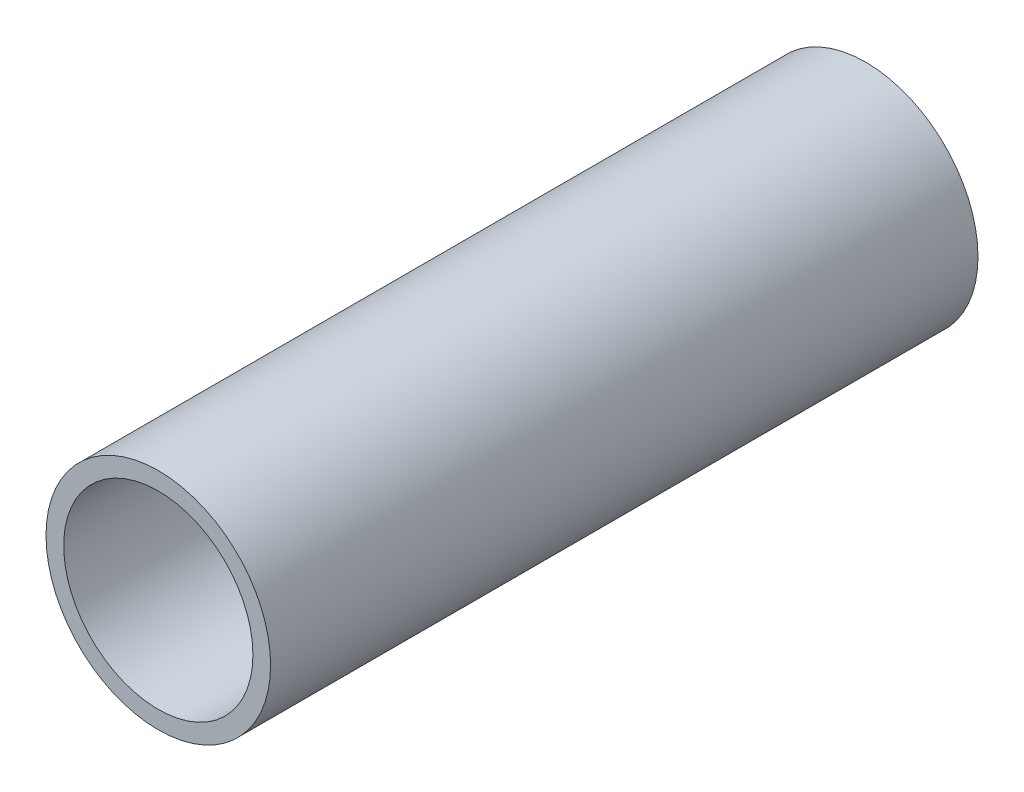
SolidWorks part; units mm, degrees
material "Hexcel AS4C (3000 Filaments)"
ref_plane "Front Plane" through (0, 0, 0) normal (0, 0, 1) x (1, 0, 0)
ref_plane "Top Plane" through (0, 0, 0) normal (0, 1, 0) x (1, 0, 0)
ref_plane "Right Plane" through (0, 0, 0) normal (1, 0, 0) x (0, 0, -1)
sketch "Sketch1" plane through (0, 0, 0) normal (0, 0, 1) x (1, 0, 0)
  circle A0 centre (0, 0) radius 12.7
  circle A1 centre (0, 0) radius 10.7
  dimension "D1" = 25.4
  dimension "D2" = 2
extrude "Boss-Extrude1" add sketch "Sketch1" along normal blind 80
